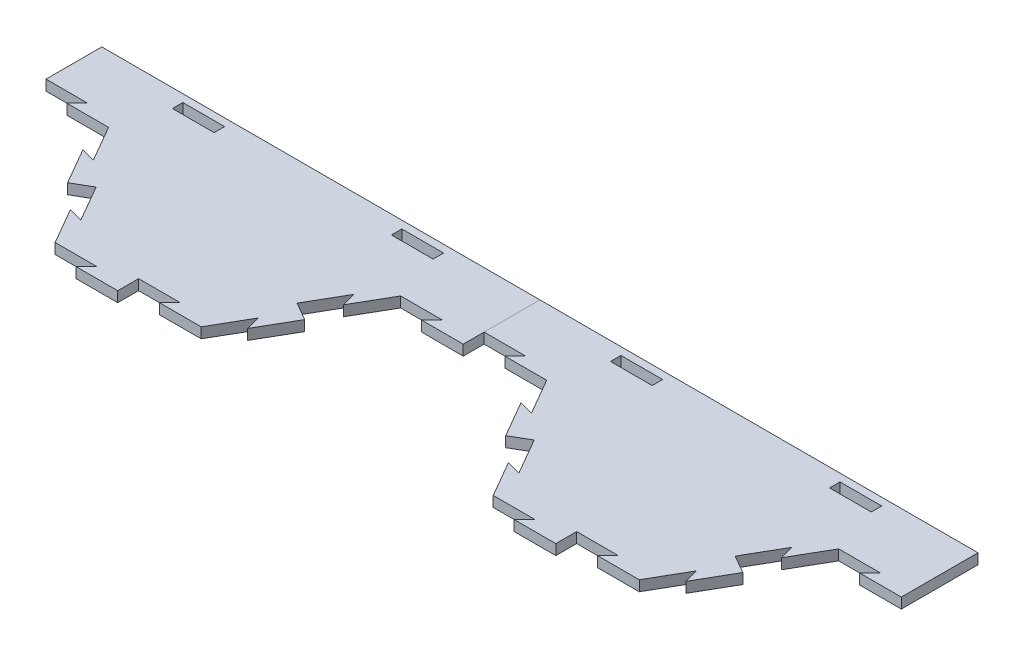
SolidWorks part; units mm, degrees
material "Cedar"
ref_plane "Front Plane" through (0, 0, 0) normal (0, 0, 1) x (1, 0, 0)
ref_plane "Top Plane" through (0, 0, 0) normal (0, 1, 0) x (1, 0, 0)
ref_plane "Right Plane" through (0, 0, 0) normal (1, 0, 0) x (0, 0, -1)
sketch "Sketch1" plane through (0, 0, 0) normal (0, 1, 0) x (1, 0, 0)
  line L0 (0, 0) -> (88.9, 0) construction
  line L1 (88.9, 0) -> (44.45, 76.9897)
  line L2 (44.45, 76.9897) -> (-44.45, 76.9897)
  line L3 (-44.45, 76.9897) -> (-88.9, 0)
  line L4 (-88.9, 0) -> (-44.45, -76.9897)
  line L5 (-44.45, -76.9897) -> (44.45, -76.9897)
  line L6 (44.45, -76.9897) -> (88.9, 0)
  circle A0 centre (0, 0) radius 76.9897 construction
  dimension "D1" = 88.9
extrude "Boss-Extrude1" add sketch "Sketch1" against normal blind 6.35
sketch "Sketch2" plane through (0, 0, 0) normal (0, 1, 0) x (1, 0, 0)
  point P1 (0, 0)
ref_axis "Axis1" through (0, 0, 0) along (0, 1, 0)
sketch "Sketch10" plane through (0, 0, 0) normal (0, 1, 0) x (1, 0, 0)
  line L0 (44.45, 76.9897) -> (57.15, 54.9926) construction
  line L1 (57.15, 54.9926) -> (48.4757, 57.3169)
  line L2 (48.4757, 57.3169) -> (61.1757, 35.3198)
  line L3 (61.1757, 35.3198) -> (66.675, 38.4948)
  line L4 (57.15, 54.9926) -> (66.675, 38.4948)
  line L5 (88.9, 0) -> (44.45, 76.9897) construction
  dimension "D1" = 45
  dimension "D2" = 6.35
extrude "Cut-Extrude4" cut sketch "Sketch10" against normal through all
sketch "Sketch11" plane through (0, 0, 0) normal (0, 1, 0) x (1, 0, 0)
  line L0 (66.675, 38.4948) -> (88.9, 0) construction
  line L1 (66.675, 38.4948) -> (72.1743, 41.6698)
  line L2 (72.1743, 41.6698) -> (84.8743, 19.6728)
  line L3 (84.8743, 19.6728) -> (76.2, 21.997)
  line L4 (76.2, 21.997) -> (66.675, 38.4948)
  line L5 (76.2, 21.997) -> (88.9, 0) construction
  line L6 (76.2, 21.997) -> (88.9, 0) construction
  line L7 (88.9, 0) -> (66.675, 38.4948) construction
  line L8 (44.45, -76.9897) -> (88.9, 0) construction
  dimension "D1" = 45
  dimension "D2" = 6.35
extrude "Boss-Extrude4" add sketch "Sketch11" against normal blind 6.35
pattern_circular "CirPattern7" count 6 over 360 about axis through (0, 0, 0) along (0, 1, 0) of "Cut-Extrude4", "Boss-Extrude4"
sketch "Sketch12" plane through (0, 0, 0) normal (0, 1, 0) x (1, 0, 0)
  line L0 (-88.9, 0) -> (88.9, 0)
  line L1 (88.9, 0) -> (88.9, 83.3397)
  line L2 (88.9, 83.3397) -> (-88.9, 83.3397)
  line L3 (-88.9, 83.3397) -> (-88.9, 0)
extrude "Cut-Extrude5" cut sketch "Sketch12" against normal through all
sketch "Sketch13" plane through (0, 0, 0) normal (0, 0, -1) x (-1, 0, 0)
  line L0 (0, -6.35) -> (0, 0) construction
  line L1 (133.35, -6.35) -> (-133.35, -6.35)
  line L2 (133.35, -6.35) -> (133.35, 0)
  line L3 (133.35, 0) -> (-133.35, 0)
  line L4 (-133.35, -6.35) -> (-133.35, 0)
  line L5 (88.9, -6.35) -> (-88.9, -6.35) construction
  dimension "D1" = 266.7
extrude "Boss-Extrude5" add sketch "Sketch13" along normal blind 40.3279
sketch "Sketch15" plane through (0, 0, 0) normal (0, 1, 0) x (1, 0, 0)
  line L0 (-88.9, 0) -> (-114.3, 0) construction
  line L1 (-114.3, 0) -> (-107.95, 6.35)
  line L2 (-107.95, 6.35) -> (-133.35, 6.35)
  line L3 (-133.35, 6.35) -> (-133.35, 0)
  line L4 (-114.3, 0) -> (-133.35, 0)
  line L6 (-133.35, 0) -> (-88.9, 0) construction
  line L7 (-133.35, 40.3279) -> (-133.35, 0) construction
  dimension "D1" = 45
  dimension "D2" = 6.35
extrude "Cut-Extrude6" cut sketch "Sketch15" against normal through all
sketch "Sketch16" plane through (0, 0, 0) normal (0, 1, 0) x (1, 0, 0)
  line L0 (88.9, 0) -> (114.3, 0) construction
  line L1 (114.3, 0) -> (107.95, -6.35)
  line L2 (107.95, -6.35) -> (133.35, -6.35)
  line L3 (133.35, -6.35) -> (133.35, 0)
  line L4 (114.3, 0) -> (133.35, 0)
  dimension "D1" = 45
  dimension "D2" = 6.35
extrude "Boss-Extrude6" add sketch "Sketch16" against normal up to surface (6.35 mm away) up to face at (-7.9375, -6.35, 35.1607)
sketch "Sketch17" plane through (0, 0, 0) normal (0, 1, 0) x (1, 0, 0)
  line L0 (0, 40.3279) -> (0, 24.6809) construction
  line L1 (-66.675, 32.5044) -> (66.675, 32.5044) construction
  line L2 (-79.375, 35.6794) -> (-53.975, 35.6794)
  line L3 (-79.375, 35.6794) -> (-79.375, 29.3294)
  line L4 (-79.375, 29.3294) -> (-53.975, 29.3294)
  line L5 (-53.975, 35.6794) -> (-53.975, 29.3294)
  line L6 (-79.375, 35.6794) -> (-53.975, 29.3294) construction
  line L7 (-79.375, 29.3294) -> (-53.975, 35.6794) construction
  line L8 (53.975, 35.6794) -> (79.375, 35.6794)
  line L9 (53.975, 35.6794) -> (53.975, 29.3294)
  line L10 (53.975, 29.3294) -> (79.375, 29.3294)
  line L11 (79.375, 35.6794) -> (79.375, 29.3294)
  line L12 (53.975, 35.6794) -> (79.375, 29.3294) construction
  line L13 (53.975, 29.3294) -> (79.375, 35.6794) construction
  line L14 (-133.35, 40.3279) -> (133.35, 40.3279) construction
  line L15 (-133.35, 24.6809) -> (133.35, 24.6809) construction
  line L16 (-133.35, 40.3279) -> (-133.35, 6.35) construction
  line L17 (133.35, 40.3279) -> (133.35, -6.35) construction
  point P4 (0, 32.5044)
  point P5 (0, 32.5044)
  dimension "D1" = 6.35
  dimension "D2" = 25.4
  dimension "D3" = 6.35
  dimension "D4" = 25.4
  dimension "D5" = 133.35
  dimension "D6" = 15.6471
extrude "Cut-Extrude8" cut sketch "Sketch17" against normal through all
pattern_linear "LPattern1" count 2 spacing 266.7 along (1, 0, 0) of bodies 135
